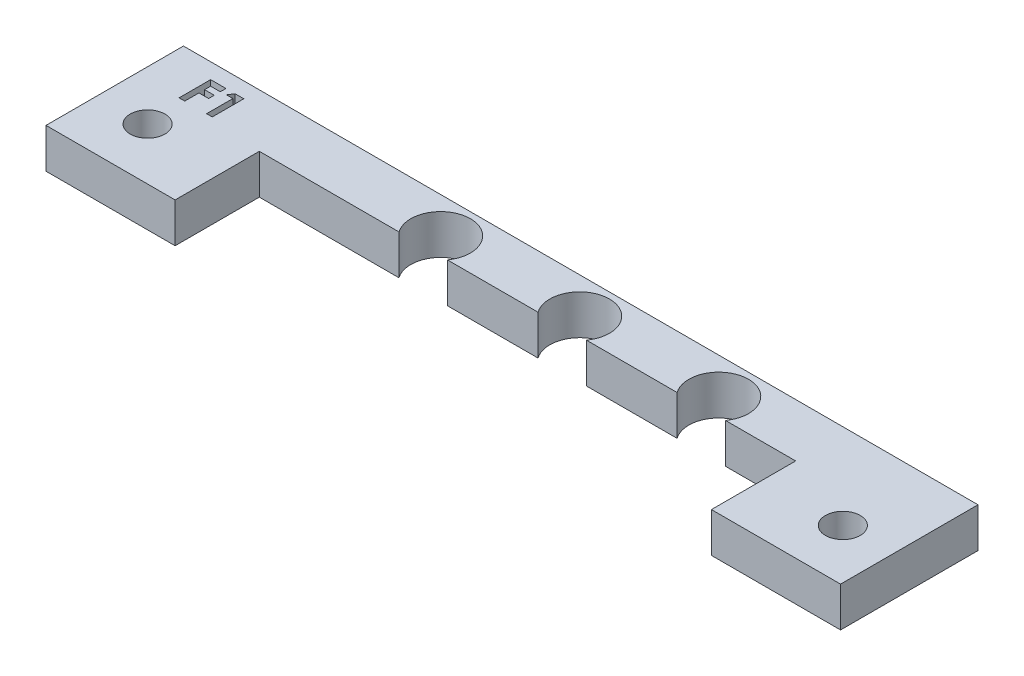
SolidWorks part; units mm, degrees
ref_plane "Front Plane" through (0, 0, 0) normal (0, 0, 1) x (1, 0, 0)
ref_plane "Top Plane" through (0, 0, 0) normal (0, 1, 0) x (1, 0, 0)
ref_plane "Right Plane" through (0, 0, 0) normal (1, 0, 0) x (0, 0, -1)
sketch "Sketch1" plane through (0, 0, 0) normal (0, 1, 0) x (1, 0, 0)
  line L0 (-6.6202, -26.3374) -> (-19.6202, -26.3374)
  line L1 (-19.6202, -26.3374) -> (-19.6202, -0.8374)
  line L2 (-19.6202, -0.8374) -> (0.3798, -0.8374)
  line L3 (47.3798, -0.8374) -> (60.3798, -0.8374)
  line L4 (60.3798, -0.8374) -> (60.3798, -26.3374)
  line L5 (60.3798, -26.3374) -> (40.3798, -26.3374)
  line L6 (-2.8702, -25.3374) -> (36.6298, -25.3374)
  line L7 (-14.6202, -0.8374) -> (-14.6202, -26.3374) construction
  line L8 (55.3798, -26.3374) -> (55.3798, -0.8374) construction
  line L9 (4.1298, -0.8374) -> (43.6298, -0.8374)
  line L10 (-19.6202, -10.3374) -> (60.3798, -10.3374) construction
  line L11 (-14.6202, -10.3374) -> (-14.6202, -0.8374)
  line L12 (-19.6202, -18.8163) -> (60.3798, -18.8163)
  line L13 (5.8798, -18.5874) -> (5.8798, -0.8374) construction
  line L14 (5.8798, -0.8374) -> (7.1198, -0.8374) construction
  line L15 (-2.8702, -26.3374) -> (40.3798, -26.3374)
  line L16 (-19.6202, -4.9779) -> (60.3798, -4.9779)
  line L17 (-19.6202, -10.3374) -> (60.3798, -10.3374)
  line L18 (47.3798, -16.8374) -> (47.3798, -26.3374)
  circle A0 centre (-14.6202, -13.5874) radius 1.75
  circle A1 centre (55.3798, -13.5874) radius 1.75
  line B0 (0.3798, -0.8374) -> (0.3798, -16.8374)
  line B1 (0.3798, -16.8374) -> (19.3798, -16.8374)
  line B2 (19.3798, -16.8374) -> (19.3798, -0.8374)
  line B3 (19.3798, -0.8374) -> (15.6298, -0.8374)
  line B4 (15.6298, -0.8374) -> (15.6298, -1.8374)
  line B5 (15.6298, -1.8374) -> (17.6298, -1.8374)
  line B6 (17.6298, -1.8374) -> (17.6298, -15.3374)
  line B7 (17.6298, -15.3374) -> (2.1298, -15.3374)
  line B8 (2.1298, -15.3374) -> (2.1298, -1.8374)
  line B9 (2.1298, -1.8374) -> (4.1298, -1.8374)
  line B10 (4.1298, -1.8374) -> (4.1298, -0.8374)
  line B11 (4.1298, -0.8374) -> (0.3798, -0.8374)
  line B12 (2.1298, -1.8374) -> (17.6298, -15.3374) construction
  line B13 (2.1298, -15.3374) -> (17.6298, -1.8374) construction
  line B14 (2.1298, -8.5874) -> (17.6298, -8.5874) construction
  line B15 (4.1298, -1.8374) -> (15.6298, -1.8374) construction
  line B16 (9.8798, -1.8374) -> (9.8798, -15.3374) construction
  circle B17 centre (9.8798, -8.5874) radius 3
  line B18 (12.3798, -26.3374) -> (12.3798, -10.3374)
  line B19 (12.3798, -10.3374) -> (-6.6202, -10.3374)
  line B20 (-6.6202, -10.3374) -> (-6.6202, -26.3374)
  line B21 (-6.6202, -26.3374) -> (-2.8702, -26.3374)
  line B22 (-2.8702, -26.3374) -> (-2.8702, -25.3374)
  line B23 (-2.8702, -25.3374) -> (-4.8702, -25.3374)
  line B24 (-4.8702, -25.3374) -> (-4.8702, -11.8374)
  line B25 (-4.8702, -11.8374) -> (10.6298, -11.8374)
  line B26 (10.6298, -11.8374) -> (10.6298, -25.3374)
  line B27 (10.6298, -25.3374) -> (8.6298, -25.3374)
  line B28 (8.6298, -25.3374) -> (8.6298, -26.3374)
  line B29 (8.6298, -26.3374) -> (12.3798, -26.3374)
  line B30 (10.6298, -25.3374) -> (-4.8702, -11.8374) construction
  line B31 (10.6298, -11.8374) -> (-4.8702, -25.3374) construction
  line B32 (10.6298, -18.5874) -> (-4.8702, -18.5874) construction
  line B33 (8.6298, -25.3374) -> (-2.8702, -25.3374) construction
  line B34 (2.8798, -25.3374) -> (2.8798, -11.8374) construction
  circle B35 centre (2.8798, -18.5874) radius 3
  line B36 (28.3798, -0.8374) -> (28.3798, -16.8374)
  line B37 (28.3798, -16.8374) -> (47.3798, -16.8374)
  line B38 (47.3798, -16.8374) -> (47.3798, -0.8374)
  line B39 (47.3798, -0.8374) -> (43.6298, -0.8374)
  line B40 (43.6298, -0.8374) -> (43.6298, -1.8374)
  line B41 (43.6298, -1.8374) -> (45.6298, -1.8374)
  line B42 (45.6298, -1.8374) -> (45.6298, -15.3374)
  line B43 (45.6298, -15.3374) -> (30.1298, -15.3374)
  line B44 (30.1298, -15.3374) -> (30.1298, -1.8374)
  line B45 (30.1298, -1.8374) -> (32.1298, -1.8374)
  line B46 (32.1298, -1.8374) -> (32.1298, -0.8374)
  line B47 (32.1298, -0.8374) -> (28.3798, -0.8374)
  line B48 (30.1298, -1.8374) -> (45.6298, -15.3374) construction
  line B49 (30.1298, -15.3374) -> (45.6298, -1.8374) construction
  line B50 (30.1298, -8.5874) -> (45.6298, -8.5874) construction
  line B51 (32.1298, -1.8374) -> (43.6298, -1.8374) construction
  line B52 (37.8798, -1.8374) -> (37.8798, -15.3374) construction
  circle B53 centre (37.8798, -8.5874) radius 3
  line B54 (14.3798, -0.8374) -> (14.3798, -16.8374)
  line B55 (14.3798, -16.8374) -> (33.3798, -16.8374)
  line B56 (33.3798, -16.8374) -> (33.3798, -0.8374)
  line B57 (33.3798, -0.8374) -> (29.6298, -0.8374)
  line B58 (29.6298, -0.8374) -> (29.6298, -1.8374)
  line B59 (29.6298, -1.8374) -> (31.6298, -1.8374)
  line B60 (31.6298, -1.8374) -> (31.6298, -15.3374)
  line B61 (31.6298, -15.3374) -> (16.1298, -15.3374)
  line B62 (16.1298, -15.3374) -> (16.1298, -1.8374)
  line B63 (16.1298, -1.8374) -> (18.1298, -1.8374)
  line B64 (18.1298, -1.8374) -> (18.1298, -0.8374)
  line B65 (18.1298, -0.8374) -> (14.3798, -0.8374)
  line B66 (16.1298, -1.8374) -> (31.6298, -15.3374) construction
  line B67 (16.1298, -15.3374) -> (31.6298, -1.8374) construction
  line B68 (16.1298, -8.5874) -> (31.6298, -8.5874) construction
  line B69 (18.1298, -1.8374) -> (29.6298, -1.8374) construction
  line B70 (23.8798, -1.8374) -> (23.8798, -15.3374) construction
  circle B71 centre (23.8798, -8.5874) radius 3
  line B72 (40.3798, -26.3374) -> (40.3798, -10.3374)
  line B73 (40.3798, -10.3374) -> (21.3798, -10.3374)
  line B74 (21.3798, -10.3374) -> (21.3798, -26.3374)
  line B75 (21.3798, -26.3374) -> (25.1298, -26.3374)
  line B76 (25.1298, -26.3374) -> (25.1298, -25.3374)
  line B77 (25.1298, -25.3374) -> (23.1298, -25.3374)
  line B78 (23.1298, -25.3374) -> (23.1298, -11.8374)
  line B79 (23.1298, -11.8374) -> (38.6298, -11.8374)
  line B80 (38.6298, -11.8374) -> (38.6298, -25.3374)
  line B81 (38.6298, -25.3374) -> (36.6298, -25.3374)
  line B82 (36.6298, -25.3374) -> (36.6298, -26.3374)
  line B83 (36.6298, -26.3374) -> (40.3798, -26.3374)
  line B84 (38.6298, -25.3374) -> (23.1298, -11.8374) construction
  line B85 (38.6298, -11.8374) -> (23.1298, -25.3374) construction
  line B86 (38.6298, -18.5874) -> (23.1298, -18.5874) construction
  line B87 (36.6298, -25.3374) -> (25.1298, -25.3374) construction
  line B88 (30.8798, -25.3374) -> (30.8798, -11.8374) construction
  circle B89 centre (30.8798, -18.5874) radius 3
  line B90 (26.3798, -26.3374) -> (26.3798, -10.3374)
  line B91 (26.3798, -10.3374) -> (7.3798, -10.3374)
  line B92 (7.3798, -10.3374) -> (7.3798, -26.3374)
  line B93 (7.3798, -26.3374) -> (11.1298, -26.3374)
  line B94 (11.1298, -26.3374) -> (11.1298, -25.3374)
  line B95 (11.1298, -25.3374) -> (9.1298, -25.3374)
  line B96 (9.1298, -25.3374) -> (9.1298, -11.8374)
  line B97 (9.1298, -11.8374) -> (24.6298, -11.8374)
  line B98 (24.6298, -11.8374) -> (24.6298, -25.3374)
  line B99 (24.6298, -25.3374) -> (22.6298, -25.3374)
  line B100 (22.6298, -25.3374) -> (22.6298, -26.3374)
  line B101 (22.6298, -26.3374) -> (26.3798, -26.3374)
  line B102 (24.6298, -25.3374) -> (9.1298, -11.8374) construction
  line B103 (24.6298, -11.8374) -> (9.1298, -25.3374) construction
  line B104 (24.6298, -18.5874) -> (9.1298, -18.5874) construction
  line B105 (22.6298, -25.3374) -> (11.1298, -25.3374) construction
  line B106 (16.8798, -25.3374) -> (16.8798, -11.8374) construction
  circle B107 centre (16.8798, -18.5874) radius 3
  dimension "D1" = 80
  dimension "D2" = 25.5
  dimension "D3" = 5
  dimension "D4" = 5
  dimension "D5" = 7
  dimension "D6" = 13
  dimension "D7" = 7
  dimension "D8" = 7
  dimension "D9" = 7
  dimension "D10" = 7
  dimension "D11" = 13
sketch_block_instance "Block1-1"
sketch_block "Block1" parameters "D1"=13, "D2"=15, "D3"=2, "D4"=1.75, "D5"=2, "D6"=2, "D7"=2, "D8"=2, "D9"=13.0756, "D10"=17, "D11"=17, "D12"=18.7479, "D13"=13, "D14"=2
sketch_block_instance "Block1-2"
sketch_block_instance "Block1-3"
sketch_block_instance "Block1-4"
sketch_block_instance "Block1-5"
sketch_block_instance "Block1-6"
extrude "Boss-Extrude1" add sketch "Sketch1" along normal blind 4 contours B20 L17 L1 L12 A0 | B0 L16 L11 L17 | L1 L17 L11 L16 | L17 B8 L16 B0 | B54 L16 B8 L17 B19 B17 | L17 B62 L16 B54 | B62 L17 B6 L16 | L16 B6 L17 B2 | B71 L17 B73 B36 L16 B2 | L17 B44 L16 B36 | B60 L16 B44 L17 | L16 B60 L17 B56 | B56 L17 B53 B42 L16 | L16 B42 L17 B38 | B38 L17 L4 L16 | B38 L18 L12 L4 L17 A1 region at (-12.9768, 0, 14.6715) region at (-7.1202, 0, 7.6577) region at (-17.1202, 0, 7.6577) region at (1.2548, 0, 7.6577) region at (2.2635, 0, 7.6577) region at (15.2548, 0, 7.6577) region at (16.8798, 0, 7.6577) region at (18.5048, 0, 7.6577) region at (23.8798, 0, 5.0827) region at (29.2548, 0, 7.6577) region at (30.8798, 0, 7.6577) region at (32.5048, 0, 7.6577) region at (39.5048, 0, 5.1116) region at (53.7363, 0, 14.6715) region at (46.5048, 0, 7.6577) region at (53.8798, 0, 7.6577)
sketch "Sketch2" plane through (0, 4, 0) normal (0, 1, 0) x (1, 0, 0)
  text T0 "<b>F1</b>"
extrude "Cut-Extrude1" cut sketch "Sketch2" against normal blind 1
